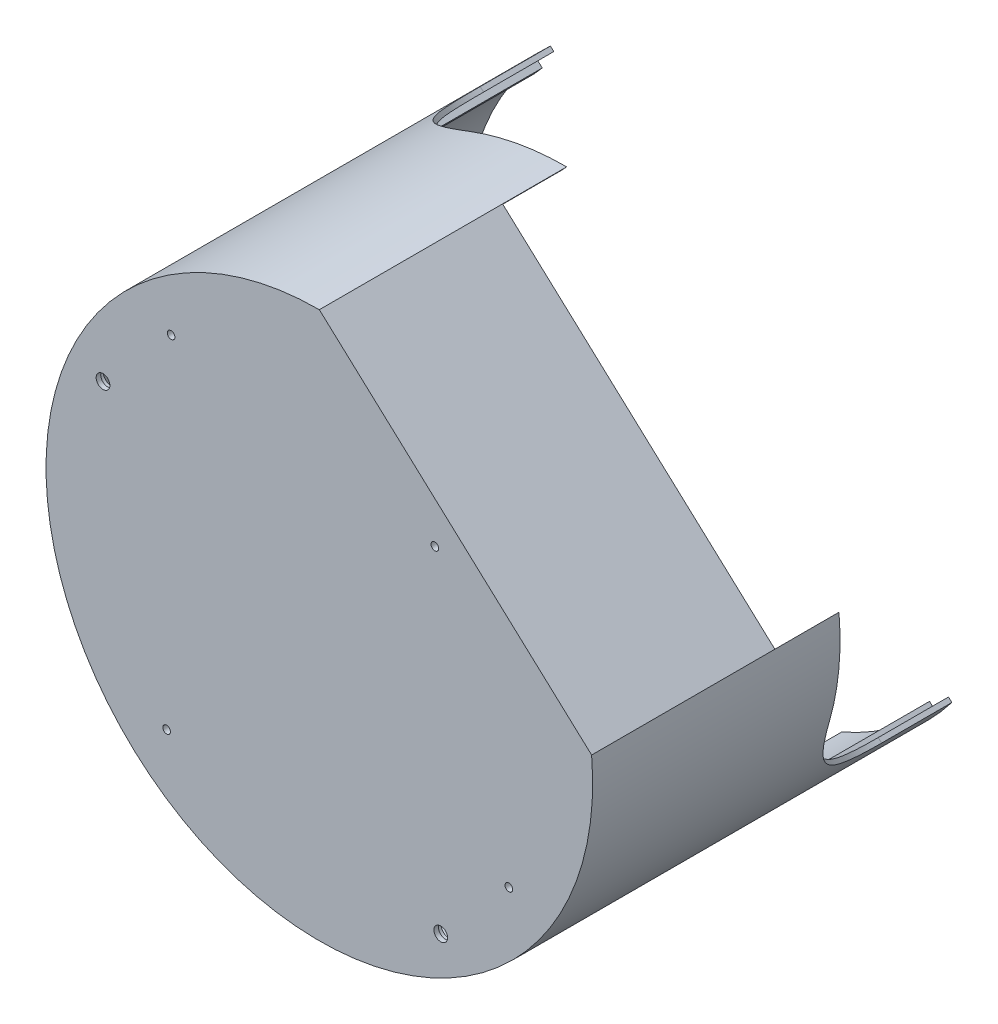
SolidWorks part; units mm, degrees
material "尼龙 101"
ref_plane "前视基准面" through (0, 0, 0) normal (0, 0, 1) x (1, 0, 0)
ref_plane "上视基准面" through (0, 0, 0) normal (0, 1, 0) x (1, 0, 0)
ref_plane "右视基准面" through (0, 0, 0) normal (1, 0, 0) x (0, 0, -1)
sketch "草图1" plane through (0, 0, 0) normal (0, 0, 1) x (1, 0, 0)
  line L0 (0, 0) -> (89.1594, 7.8004) construction
  line L1 (0, 89.5) -> (0, 0) construction
  line L2 (-0.5812, 87.9981) -> (87.7139, 7.0905)
  line L3 (89.1594, 7.8004) -> (0, 89.5)
  arc A0 (-0.5812, 87.9981) -> (87.7139, 7.0905) centre (0, 0) ccw
  arc A1 (0, 89.5) -> (89.1594, 7.8004) centre (0, 0) ccw
  dimension "D1" = 176
  dimension "D2" = 179
  dimension "D4" = 1.5
  dimension "D3" = 85
extrude "拉伸1" add sketch "草图1" along normal blind 136
sketch "草图2" plane through (44.5797, 48.6502, 0) normal (0.6756, 0.7373, 0) x (0.7373, -0.6756, 0)
  line L0 (60.4653, -136) -> (60.4653, 0) construction
  line L1 (60.4653, -76) -> (-60.4653, -76)
  line L2 (60.4653, -76) -> (60.4653, 0)
  line L3 (60.4653, 0) -> (-60.4653, 0)
  line L4 (-60.4653, -76) -> (-60.4653, 0)
  line L5 (60.4653, -136) -> (-60.4653, -136) construction
  dimension "D1" = 60
extrude "拉伸2" cut sketch "草图2" against normal up to next
ref_plane "基准面1" through (0, 0, 26) normal (0, 0, 1) x (1, 0, 0)
sketch "草图7" plane through (0, 0, 136) normal (0, 0, 1) x (1, 0, 0)
  line L1 (0, 0) -> (65.8064, 65.8064) construction
  line L3 (0, 0) -> (-90.2025, -98.4387) construction
  line L4 (0, 0) -> (8.4344, -87.5949) construction
  arc A1 (-0.5812, 87.9981) -> (87.7139, 7.0905) centre (0, 0) ccw construction
  dimension "D1" = 48
sketch "草图10" plane through (0, 0, 136) normal (0, 0, 1) x (1, 0, 0)
  line L0 (0, 0) -> (87.3785, -19.3713) construction
  line L1 (0, 0) -> (-26.9132, 85.3577) construction
  line L2 (0, 0) -> (44.5797, 48.6502) construction
  line L3 (89.1594, 7.8004) -> (0, 89.5) construction
  arc A0 (0, 89.5) -> (89.1594, 7.8004) centre (0, 0) ccw construction
  dimension "D1" = 120
  dimension "D2" = 60
ref_plane "基准面7" through (0, 0, 0) normal (-0.7373, 0.6756, 0) x (0, 0, 1)
ref_plane "基准面8" through (-60.4653, -65.9863, 136) normal (-0.6756, -0.7373, 0) x (0.7373, -0.6756, 0)
sketch "草图15" plane through (0, 0, 136) normal (0, 0, 1) x (1, 0, 0)
  line L0 (89.1594, 7.8004) -> (0, 89.5) construction
  line L1 (89.1594, 7.8004) -> (0, 89.5)
  arc A2 (0, 89.5) -> (89.1594, 7.8004) centre (0, 0) ccw construction
  arc A3 (0, 89.5) -> (89.1594, 7.8004) centre (0, 0) ccw
extrude "拉伸11" add sketch "草图15" against normal blind 3
sketch "Sketch3" plane through (-60.4653, -65.9863, 136) normal (-0.6756, -0.7373, 0) x (0.7373, -0.6756, 0)
  line L0 (45, -30) -> (45, -55) construction
  line L1 (55, -30) -> (55, -55)
  line L2 (35, -30) -> (35, -55)
  line L3 (89.5, 0) -> (-89.5, 0) construction
  arc A0 (55, -30) -> (35, -30) centre (45, -30) ccw
  arc A1 (35, -55) -> (55, -55) centre (45, -55) ccw
  point P2 (45, -42.5)
  point P9 (0, 0)
  dimension "D2" = 10
  dimension "D1" = 45
  dimension "D3" = 25
  dimension "D4" = 30
extrude "Extrude5" cut sketch "Sketch3" against normal up to next
mirror "Mirror2" about plane through (0, 0, 0) normal (-0.7373, 0.6756, 0) of "Extrude5"
sketch "草图16" plane through (0, 0, 136) normal (0, 0, 1) x (1, 0, 0)
  line L0 (0, 0) -> (51.1074, 55.774) construction
  line L1 (0, 0) -> (-80.0434, 73.3463) construction
  line L2 (0, 0) -> (108.7277, -69.2672) construction
  line L3 (0, 0) -> (-76.4646, 99.6507) construction
  line L4 (0, 0) -> (-111.3102, -57.9444) construction
  line L5 (0, 0) -> (-42.7518, -103.2119) construction
  circle A0 centre (0, 0) radius 60 construction
  circle A1 centre (0, 0) radius 25 construction
  circle A2 centre (-36.5257, 47.6012) radius 27.5 construction
  circle A3 centre (50.6035, -32.238) radius 27.5 construction
  arc A4 (-50.4586, -55.0659) -> (-25.7231, -28.0718) centre (-22.961, -55.4328) ccw construction
  arc A5 (-25.7231, -28.0718) -> (-50.4586, -55.0659) centre (-53.2206, -27.7049) ccw construction
  circle A6 centre (39.7572, -67.6266) radius 2.25
  circle A7 centre (-70.8344, 33.7119) radius 2.25
  dimension "D5" = 120
  dimension "D6" = 50
  dimension "D7" = 55
  dimension "D8" = 55
  dimension "D9" = 55
  dimension "D10" = 55
  dimension "D11" = 23
  dimension "D12" = 23
  dimension "D13" = 4.5
  dimension "D15" = 150
  dimension "D16" = 75
  dimension "D1" = 10
  dimension "D2" = 10
  dimension "D3" = 20
  dimension "D4" = 20
extrude "拉伸12" cut sketch "草图16" against normal blind 1.5
sketch "草图17" plane through (0, 0, 134.5) normal (0, 0, 1) x (1, 0, 0)
  line L0 (-70.8344, 33.7119) -> (39.7572, -67.6266) construction
  circle A0 centre (-70.8344, 33.7119) radius 3
  circle A1 centre (39.7572, -67.6266) radius 3
extrude "拉伸13" cut sketch "草图17" against normal blind 2
sketch "草图18" plane through (-60.4653, -65.9863, 136) normal (-0.6756, -0.7373, 0) x (0.7373, -0.6756, 0)
  line L0 (89.5, 0) -> (-89.5, 0) construction
  line L1 (-37.7889, -115) -> (-37.7889, -140) construction
  line L3 (-81.7889, -140) -> (-81.7889, -115) construction
  line L4 (-81.7889, -115) -> (-37.7889, -115) construction
  line L5 (-81.7889, -115) -> (-81.7889, -140)
  line L6 (-81.7889, -140) -> (-37.7889, -140)
  line L7 (-37.7889, -140) -> (-37.7889, -115)
  arc A0 (-78.2644, -93.0682) -> (-81.7889, -115) centre (-11.7889, -115) ccw
  arc A1 (-37.7889, -115) -> (-54.9034, -84.915) centre (-72.7889, -115) ccw
  arc A3 (-54.9034, -84.915) -> (-78.2644, -93.0682) centre (-63.7889, -97) ccw
  spline S1 degree 3 poles (-81.7889, -115) (-81.7889, -112.8074) (-81.7083, -110.6558) (-81.4664, -107.486) (-81.3654, -106.4391) (-81.1806, -104.8835) (-81.1133, -104.3661) (-80.9685, -103.3467) (-80.891, -102.8439) (-80.477, -100.3628) (-80.063, -98.4831) (-79.2946, -95.8148) (-79.0122, -94.9472) (-78.4032, -93.2949) (-78.0761, -92.5069) (-77.3729, -91.0051) (-76.9969, -90.2912) (-76.1909, -88.9374) (-75.7603, -88.2967) (-74.3819, -86.4947) (-73.3732, -85.4847) (-71.7075, -84.2481) (-71.1267, -83.8827) (-69.9097, -83.2485) (-69.2703, -82.9793) (-67.3088, -82.3385) (-65.9319, -82.124) (-64.121, -82.1209) (-63.7543, -82.1337) (-63.0117, -82.1864) (-62.6347, -82.2265) (-61.4992, -82.3873) (-60.7377, -82.5477) (-58.4418, -83.1825) (-56.8957, -83.809) (-54.565, -85.0591) (-53.7957, -85.523) (-52.2842, -86.5361) (-51.5403, -87.0861) (-50.0788, -88.2723) (-49.3611, -88.9085) (-48.3073, -89.9288) (-47.9589, -90.2809) (-47.2757, -91.0019) (-46.9409, -91.3707) (-45.3005, -93.256) (-44.096, -94.8948) (-42.7443, -97.111) (-42.4817, -97.5628) (-41.9729, -98.4836) (-41.7261, -98.9539) (-41.0187, -100.3772) (-40.5891, -101.3453) (-39.4292, -104.3069) (-38.8265, -106.3573) (-38.3112, -109.0224) (-38.22, -109.5618) (-38.0637, -110.6422) (-37.9985, -111.1838) (-37.8417, -112.8125) (-37.7889, -113.9035) (-37.7889, -115) knots 0 0 0 0 0.0625 0.0625 0.09375 0.09375 0.109375 0.109375 0.125 0.125 0.1875 0.1875 0.21875 0.21875 0.25 0.25 0.28125 0.28125 0.3125 0.3125 0.375 0.375 0.40625 0.40625 0.4375 0.4375 0.5 0.5 0.515625 0.515625 0.53125 0.53125 0.5625 0.5625 0.625 0.625 0.65625 0.65625 0.6875 0.6875 0.71875 0.71875 0.734375 0.734375 0.75 0.75 0.8125 0.8125 0.828125 0.828125 0.84375 0.84375 0.875 0.875 0.9375 0.9375 0.953125 0.953125 0.96875 0.96875 1 1 1 1 construction
  point P7 (0, 0)
  dimension "D1" = 70
  dimension "D2" = 140
  dimension "D3" = 30
  dimension "D4" = 44
  dimension "D8" = 43
  dimension "D9" = 18
  dimension "D5" = 38
  dimension "D6" = 25
  dimension "D7" = 140
extrude "拉伸19" [suppressed] cut sketch "草图18" against normal up to surface (20.7278 mm away)
mirror "镜向4" [suppressed] about plane through (0, 0, 0) normal (-0.7373, 0.6756, 0)
ref_plane "基准面10" through (44.5797, -40.8498, 0) normal (0.7373, -0.6756, 0) x (0, 0, -1)
sketch "草图22" plane through (44.5797, -40.8498, 0) normal (0.7373, -0.6756, 0) x (0, 0, -1)
  line L0 (-136, 65.9863) -> (-76, 65.9863) construction
  line L1 (-23, 7.9863) -> (5, 7.9863)
  line L3 (-55, 39.9863) -> (-55, 65.9863)
  line L4 (-55, 65.9863) -> (5, 65.9863)
  line L5 (5, 65.9863) -> (5, 7.9863)
  arc A0 (-55, 39.9863) -> (-23, 7.9863) centre (-23, 39.9863) ccw
  dimension "D1" = 26
  dimension "D6" = 141
  dimension "D4" = 58
  dimension "D5" = 60
extrude "拉伸22" cut sketch "草图22" along normal blind 52 and the other way blind 10 contours L5 L1 A0 L3 L4
mirror "镜向6" about plane through (0, 0, 0) normal (-0.7373, 0.6756, 0) of "拉伸22"
sketch "草图28" plane through (0, 0, 133) normal (0, 0, -1) x (-1, 0, 0)
  line L0 (-42.0918, 48.8955) -> (-45.0409, 46.1931)
  line L1 (-87.7139, 7.0905) -> (0.5812, 87.9981) construction
  line L2 (-45.0409, 46.1931) -> (-43.6897, 44.7186)
  line L3 (-43.6897, 44.7186) -> (-40.7406, 47.4209)
  line L4 (-40.7406, 47.4209) -> (-42.0918, 48.8955)
  point P4 (-43.5663, 47.5443)
  dimension "D1" = 4
  dimension "D2" = 2
  dimension "D3" = 2
extrude "拉伸25" add sketch "草图28" along normal up to surface (57 mm away) up to face at (43.7806, 47.7781, 76)
sketch "草图29" plane through (0, 0, 133) normal (0, 0, -1) x (-1, 0, 0)
  line L0 (0, 0) -> (65.3967, -58.8835) construction
  line L1 (0, 0) -> (78.057, -40.6339) construction
  line L2 (61.8116, -58.3466) -> (64.4881, -55.3741) construction
  line L3 (64.4881, -55.3741) -> (66.7641, -57.3284) construction
  line L4 (61.8116, -58.3466) -> (63.9931, -60.4059) construction
  line L5 (75.3388, -41.4737) -> (77.1858, -37.9256)
  line L6 (77.1858, -37.9256) -> (78.9808, -38.8076)
  line L7 (75.3388, -41.4737) -> (77.0909, -42.4382)
  arc A0 (77.0909, -42.4382) -> (78.9808, -38.8076) centre (0, 0) ccw
  arc A1 (63.9931, -60.4059) -> (66.7641, -57.3284) centre (0, 0) ccw construction
  point P6 (0, 0)
  point P8 (63.1498, -56.8604)
  point P13 (76.2623, -39.6996)
  dimension "D4" = 2
  dimension "D6" = 4
  dimension "D1" = 176
  dimension "D2" = 14.5
  dimension "D3" = 4
  dimension "D5" = 3
extrude "拉伸26" add sketch "草图29" along normal up to surface (133 mm away) up to face at (-27.2816, -29.7726, 0)
sketch "草图34" plane through (0, 0, 133) normal (0, 0, -1) x (-1, 0, 0)
  line L0 (-62.5121, -61.9374) -> (-61.0597, -60.5624)
  line L1 (-61.0597, -60.5624) -> (-63.8097, -57.6577)
  line L2 (-63.8097, -57.6577) -> (-65.2621, -59.0327)
  arc A0 (-87.7139, 7.0905) -> (77.0909, -42.4382) centre (0, 0) ccw construction
  arc A1 (-65.2621, -59.0327) -> (-62.5121, -61.9374) centre (0, 0) ccw
  dimension "D3" = 2
  dimension "D1" = 2
  dimension "D2" = 4
extrude "拉伸27" add sketch "草图34" along normal up to surface (133 mm away) up to face at (-46.647, -30.6936, 0)
ref_axis "基准轴2" through (0, 0, 143.25) along (0, 0, -1)
sketch "草图39" plane through (0, 0, 136) normal (0, 0, 1) x (1, 0, 0)
  line L0 (0, 0) -> (44.5797, 48.6502)
  line L1 (89.1594, 7.8004) -> (0, 89.5)
  line L2 (89.1594, 7.8004) -> (0, 89.5)
  line L3 (0, 89.5) -> (89.1594, 7.8004) construction
  arc A1 (0, 89.5) -> (89.1594, 7.8004) centre (0, 0) ccw
  arc A2 (0, 89.5) -> (89.1594, 7.8004) centre (0, 0) ccw
  dimension "D1" = 0
ref_plane "基准面12" through (0, 0, 0) normal (0.7373, -0.6756, 0) x (0, 0, -1)
mirror "镜向9" about plane through (0, 0, 0) normal (0.7373, -0.6756, 0) of "拉伸26"
mirror "镜向8" about plane through (0, 0, 0) normal (-0.7373, 0.6756, 0) of "拉伸27"
sketch "Sketch4" plane through (-60.4653, -65.9863, 136) normal (-0.6756, -0.7373, 0) x (0.7373, -0.6756, 0)
  line L0 (89.5, 0) -> (-89.5, 0) construction
  line L1 (-35.5, -10) -> (35.5, -10)
  line L2 (-37.5, -12) -> (-37.5, -23)
  line L3 (-35.5, -25) -> (35.5, -25)
  line L4 (37.5, -12) -> (37.5, -23)
  arc A0 (-37.5, -12) -> (-35.5, -10) centre (-35.5, -12) cw
  arc A1 (35.5, -10) -> (37.5, -12) centre (35.5, -12) cw
  arc A2 (37.5, -23) -> (35.5, -25) centre (35.5, -23) cw
  arc A3 (-37.5, -23) -> (-35.5, -25) centre (-35.5, -23) ccw
  point P4 (0, -10)
  point P7 (0, 0)
  point P14 (37.5, -25)
  point P17 (-37.5, -25)
  dimension "D4" = 2
  dimension "D1" = 25
  dimension "D2" = 15
  dimension "D3" = 75
extrude "Extrude6" [suppressed] cut sketch "Sketch4" against normal up to next
sketch "Sketch2" plane through (0, 0, 0) normal (0, 1, 0) x (1, 0, 0)
  line L0 (0, -23) -> (32, -23) construction
  line L1 (32, -23) -> (32, 9)
  line L2 (32, 9) -> (0, 9)
  arc A0 (0, 9) -> (32, -23) centre (0, -23) ccw
  dimension "D1" = 64
  dimension "D2" = 23
sketch "Sketch1" plane through (0, 0, 0) normal (0, 0, -1) x (-1, 0, 0)
  line L0 (60.4653, -65.9863) -> (40.1976, -43.868) construction
  line L1 (89.4905, 1.3006) -> (-9.0953, -89.0367)
  arc A0 (-9.0953, -89.0367) -> (89.4905, 1.3006) centre (0, 0) ccw
  dimension "D1" = 30
extrude "Extrude3" cut sketch "Sketch1" against normal blind 20
draft "拔模1" [suppressed] type of draft neutral plane draft angle 0.5 faces to draft 2 reverse direction yes parameters "D1"=0.5
draft "拔模2" [suppressed] type of draft neutral plane draft angle 0.5 faces to draft 22 parameters "D1"=0.5
sketch "草图35" plane through (0, 0, 136) normal (0, 0, 1) x (1, 0, 0)
  line L0 (-28.3959, 34.1395) -> (36.4845, -25.3124)
  line L1 (89.1594, 7.8004) -> (0, 89.5) construction
  line L2 (0, 0) -> (4.0443, 4.4136) construction
  line L3 (-48.6636, 12.0212) -> (16.2168, -47.4307)
  line L4 (0, 0) -> (-16.2234, -17.7047) construction
  line L5 (-70.8344, 33.7119) -> (39.7572, -67.6266) construction
  point P14 (-36.4911, -39.8231)
  dimension "D1" = 88
  dimension "D2" = 60
  dimension "D3" = 88
  dimension "D4" = 30
  dimension "D5" = 1.0137
  dimension "D6" = 120
sketch "草图37" plane through (0, 0, 136) normal (0, 0, 1) x (1, 0, 0)
  line L0 (89.1594, 7.8004) -> (0, 89.5) construction
  line L1 (62.0517, -43.2965) -> (-48.5399, 58.042) construction
  line L2 (0, 0) -> (6.7559, 7.3728) construction
  line L4 (44.5797, 48.6502) -> (37.8238, 41.2774) construction
  circle A0 centre (62.0517, -43.2965) radius 3
  circle A1 centre (-48.5399, 58.042) radius 3
  circle A4 centre (-50.0029, -54.5686) radius 3
  circle A5 centre (37.8238, 41.2774) radius 3
  dimension "D1" = 10
  dimension "D2" = 140
  dimension "D3" = 6
  dimension "D4" = 10
  dimension "D5" = 150
extrude "拉伸28" add sketch "草图37" against normal blind 6
chamfer "倒角1" distance 3 angle 10 4 edges at (-47.0029, -54.5686, 130) (40.8238, 41.2774, 130) (-45.5399, 58.042, 130) (65.0517, -43.2965, 130) first distance on face at (-47.0029, -54.5686, 130) first distance on face at (40.8238, 41.2774, 130) first distance on face at (-45.5399, 58.042, 130) first distance on face at (65.0517, -43.2965, 130)
sketch "草图40" plane through (0, 0, 136) normal (0, 0, 1) x (1, 0, 0)
  line L0 (0, 0) -> (44.5797, 48.6502)
  line L1 (89.1594, 7.8004) -> (0, 89.5) construction
  line L3 (0, 0) -> (38.8054, 38.8054)
  line L4 (0, 0) -> (89.1594, 7.8004)
sketch "草图41" plane through (0, 0, 133) normal (0, 0, -1) x (-1, 0, 0)
  line L4 (-1.9629, -44.9572) -> (1.9629, 44.9572)
ref_plane "基准面13" through (0, 0, 0) normal (0.999, 0.0436, 0) x (0, 0, -1)
sketch "草图42" plane through (0, 0, 0) normal (0.999, 0.0436, 0) x (0, 0, -1)
  line L0 (0, -1.5) -> (-23, -1.5) construction
  line L1 (-23, -34.5) -> (10, -34.5)
  line L3 (-23, 31.5) -> (10, 31.5)
  line L4 (10, 31.5) -> (10, -1.5)
  line L5 (10, -34.5) -> (10, -1.5)
  arc A0 (-23, 31.5) -> (-23, -34.5) centre (-23, -1.5) ccw
  dimension "D2" = 33
  dimension "D1" = 23
  dimension "D3" = 1.5
extrude "切除-拉伸1" cut sketch "草图42" against normal blind 100
mirror "镜向10" about plane through (0, 0, 0) normal (0.7373, -0.6756, 0) of "切除-拉伸1"
hole_wizard "M3 螺纹孔1" positions "3D草图2" profile "草图45" tap size "M3" standard "GB" end condition through all
sketch3d "3D草图2"
  point P0 (-48.5399, 58.042, 136)
  point P3 (62.0517, -43.2965, 136)
  point P6 (-50.0029, -54.5686, 136)
  point P9 (37.8238, 41.2774, 136)
sketch "草图45" plane through (-48.5399, 58.042, 136) normal (1, 0, 0) x (0, -1, 0)
  line L0 (0, 0) -> (0, 136)
  line L1 (0, 136) -> (1.25, 136)
  line L2 (1.25, 136) -> (1.25, 0)
  line L5 (1.25, 0) -> (0, 0)
  line L11 (0, -6.35) -> (0, 107.95) construction
  dimension "通孔螺纹孔钻头直径" = 2.5
  dimension "通孔螺纹孔钻头深度" = 136
cosmetic thread "孔螺蚊线1" parameters "D2"=3
cosmetic thread "孔螺蚊线2" parameters "D2"=3
cosmetic thread "孔螺蚊线3" parameters "D2"=3
cosmetic thread "孔螺蚊线4" parameters "D2"=3
